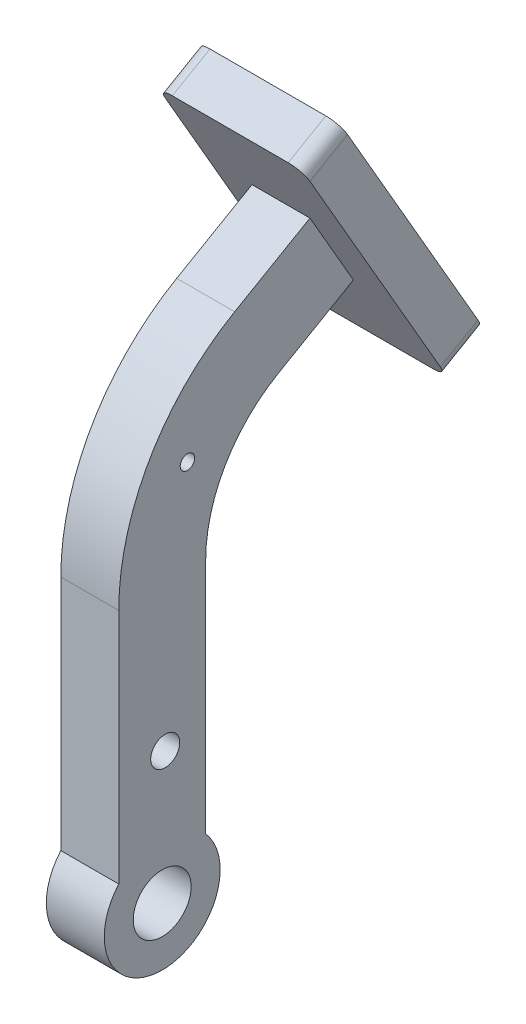
SolidWorks part; units mm, degrees
ref_plane "Front Plane" through (0, 0, 0) normal (0, 0, 1) x (1, 0, 0)
ref_plane "Top Plane" through (0, 0, 0) normal (0, 1, 0) x (1, 0, 0)
ref_plane "Right Plane" through (0, 0, 0) normal (1, 0, 0) x (0, 0, -1)
sketch "Image" plane through (0, 0, 0) normal (1, 0, 0) x (0, 0, -1)
  line L0 (294.3509, 636.9257) -> (533.3607, 636.9257) construction
sketch "Sketch3" plane through (0, 0, 0) normal (1, 0, 0) x (0, 0, -1)
  line L0 (46.4711, 217.0929) -> (96.4711, 130.4904)
  line L1 (96.4711, 130.4904) -> (83.4808, 122.9904)
  line L2 (83.4808, 122.9904) -> (33.4808, 209.5929)
  line L3 (33.4808, 209.5929) -> (46.4711, 217.0929)
  line L4 (50.9808, 179.282) -> (25, 164.282)
  line L5 (40, 138.3013) -> (65.9808, 153.3013)
  line L6 (-15, 95) -> (-15, 13.2288)
  line L7 (25, 164.282) -> (65, 95) construction
  line L8 (15, 13.2288) -> (15, 95)
  line L9 (65, 95) -> (-15, 95) construction
  line L10 (-4.282, 135) -> (21.6987, 120) construction
  arc A0 (25, 164.282) -> (-15, 95) centre (65, 95) ccw
  arc A1 (40, 138.3013) -> (15, 95) centre (65, 95) ccw
  arc A2 (-15, 13.2288) -> (15, 13.2288) centre (0, 0) ccw
  circle A3 centre (0, 0) radius 10
  circle A4 centre (1.0325, 45) radius 5
  circle A6 centre (8.7083, 127.5) radius 2.5
  dimension "D3" = 80
  dimension "D4" = 50
  dimension "D14" = 40
  dimension "D15" = 20
  dimension "D12" = 10
  dimension "D16" = 5
  dimension "D1" = 15
  dimension "D2" = 100
  dimension "D5" = 95
  dimension "D6" = 30
  dimension "D7" = 30
  dimension "D8" = 60
  dimension "D9" = 30
  dimension "D10" = 35
  dimension "D11" = 50
  dimension "D13" = 30
extrude "Boss-Extrude1" add sketch "Sketch3" along normal mid plane 20 contours L6 A2 L8 A1 L5 L2 L4 A0 A4 A3 region at (0, 86.2265, -10.1176)
extrude "Boss-Extrude2" add sketch "Sketch3<3>" along normal mid plane 50 contours L3 L2 L1 L0 region at (0, 170.0417, -64.976)
sketch "Sketch3<3>" plane through (0, 0, 0) normal (1, 0, 0) x (0, 0, -1) same geometry as "Sketch3"
fillet "Fillet1" radius 5 4 edges at (25, 213.3429, -39.976) (-25, 213.3429, -39.976) (-25, 126.7404, -89.976) (25, 126.7404, -89.976)
sketch "Sketch6" plane through (0, 74.3958, -128.8573) normal (0, 0.5, -0.866) x (-1, 0, 0)
  line L0 (-25, 114.7724) -> (25, 114.7724) construction
  line L1 (-25, 159.7724) -> (-25, 69.7724) construction
  line L2 (25, 159.7724) -> (25, 69.7724) construction
  line L3 (-10, 149.7724) -> (-10, 79.7724) construction
  line L4 (-5, 149.7724) -> (-5, 79.7724)
  line L5 (-15, 149.7724) -> (-15, 79.7724)
  line L6 (10, 149.7724) -> (10, 79.7724) construction
  line L7 (15, 149.7724) -> (15, 79.7724)
  line L8 (5, 149.7724) -> (5, 79.7724)
  arc A0 (-5, 149.7724) -> (-15, 149.7724) centre (-10, 149.7724) ccw
  arc A1 (-15, 79.7724) -> (-5, 79.7724) centre (-10, 79.7724) ccw
  arc A2 (15, 149.7724) -> (5, 149.7724) centre (10, 149.7724) ccw
  arc A3 (5, 79.7724) -> (15, 79.7724) centre (10, 79.7724) ccw
  point P8 (-10, 114.7724)
  point P15 (10, 114.7724)
  dimension "D1" = 5
  dimension "D2" = 70
  dimension "D3" = 10
  dimension "D4" = 10
  dimension "D5" = 10
extrude "Boss-Extrude4" add sketch "Sketch6" along normal blind 2
fillet "Fillet6" radius 1 8 edges at (-10, 209.4327, -53.2032) (-15, 174.7917, -73.2032) (-10, 140.1506, -93.2032) (10, 209.4327, -53.2032) (5, 174.7917, -73.2032) (10, 140.1506, -93.2032) (-5, 174.7917, -73.2032) (15, 174.7917, -73.2032)
